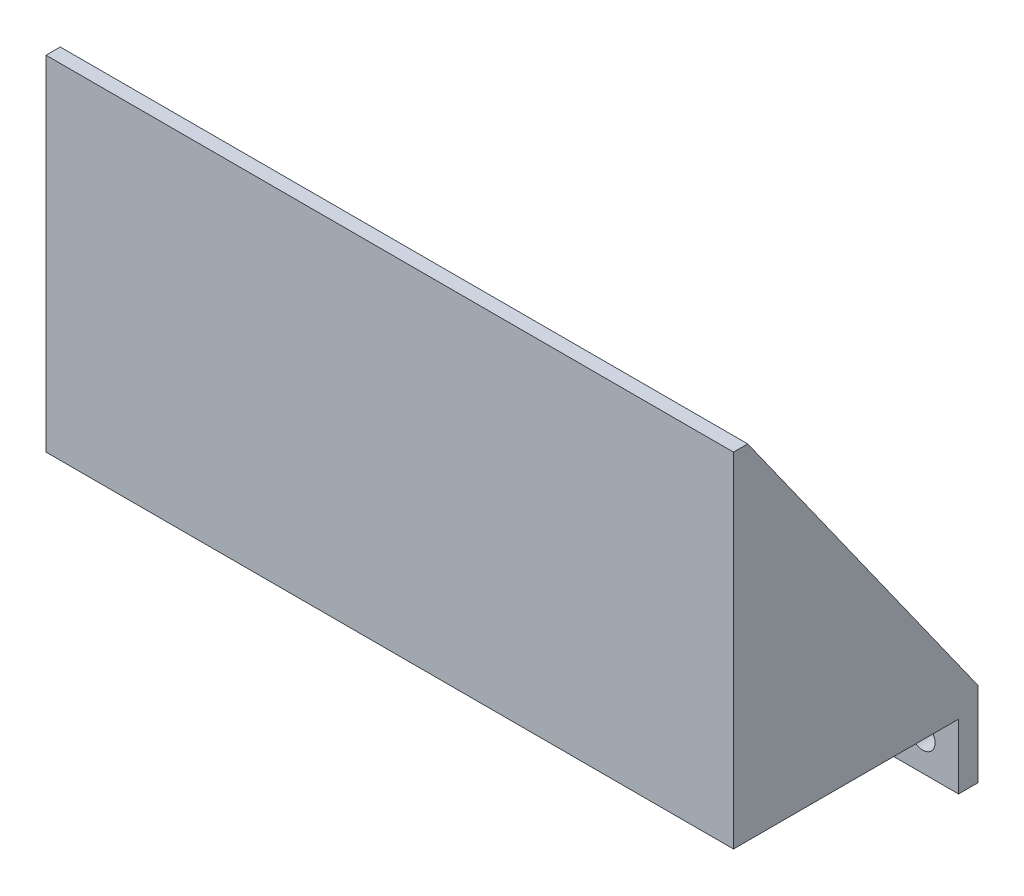
SolidWorks part; units mm, degrees
ref_plane "Front Plane" through (0, 0, 0) normal (0, 0, 1) x (1, 0, 0)
ref_plane "Top Plane" through (0, 0, 0) normal (0, 1, 0) x (1, 0, 0)
ref_plane "Right Plane" through (0, 0, 0) normal (1, 0, 0) x (0, 0, -1)
sketch "Sketch1" plane through (0, 0, 0) normal (0, 1, 0) x (1, 0, 0)
  line L0 (-3, 35.5) -> (0, 35.5)
  line L1 (0, 0) -> (100.5, 0)
  line L2 (0, 0) -> (0, 35.5)
  line L3 (0, 35.5) -> (100.5, 35.5)
  line L4 (100.5, 0) -> (100.5, 35.5)
  line L5 (-3, 35.5) -> (-3, -2.1974)
  line L6 (-3, -2.1974) -> (103, -2.1974)
  line L10 (103, 35.5) -> (100.5, 35.5)
  line L11 (103, 35.5) -> (103, -2.1974)
  line L12 (0, 35.5) -> (0, 0)
  line L13 (-3, 35.5) -> (103, 35.5)
  line L14 (-3, 35.5) -> (-3, 32.5)
  line L15 (-3, 32.5) -> (103, 32.5)
  line L16 (103, 35.5) -> (103, 32.5)
  line L17 (100.5, 35.5) -> (100.5, 0)
  line L19 (0, 35.5) -> (-3, 35.5)
  line L20 (0, 35.5) -> (0, 32.5)
  line L21 (0, 32.5) -> (-3, 32.5)
  line L22 (-3, 35.5) -> (-3, 32.5)
  line L23 (100.5, 35.5) -> (103, 35.5)
  line L24 (100.5, 35.5) -> (100.5, 32.5)
  line L25 (100.5, 32.5) -> (103, 32.5)
  line L26 (103, 35.5) -> (103, 32.5)
  dimension "D1" = 100.5
  dimension "D2" = 3
  dimension "D3" = 35.5
extrude "Boss-Extrude1" add sketch "Sketch1" along normal blind 50 contours L11 L10 L4 L1 L2 L0 L5 L6 | L20 L19 L22 L21 | L24 L23 L26 L25 region at (-1.5, 0, -31.3847)
sketch "Sketch2" plane through (0, 0, 0) normal (1, 0, 0) x (0, 0, -1)
  line L0 (35.5, 0) -> (0, 50)
  line L1 (0, 50) -> (35.5, 50)
  line L2 (35.5, 50) -> (35.5, 0)
extrude "Cut-Extrude1" cut sketch "Sketch2" against normal blind 10 and the other way blind 110
extrude "Boss-Extrude4" add sketch "Sketch1<6>" against normal blind 13 separate body contours L12 L15 L4 L3 | L5 L15 L12 L0 | L4 L15 L11 L10 region at (-1.5, 0, -34) region at (50.25, 0, -34) region at (101.75, 0, -34)
sketch "Sketch1<6>" plane through (0, 0, 0) normal (0, 1, 0) x (1, 0, 0) same geometry as "Sketch1"
extrude "Boss-Extrude5" add sketch "Sketch1<8>" against normal blind 3 contours L15 L2 L1 L4 | L15 L5 L6 L11 L4 L1 L2 region at (-1.5, 0, -31.3847) region at (50.25, 0, -16.25)
sketch "Sketch1<8>" plane through (0, 0, 0) normal (0, 1, 0) x (1, 0, 0) same geometry as "Sketch1"
sketch "Sketch3" plane through (0, 0, -32.5) normal (0, 0, 1) x (1, 0, 0)
  line L0 (50, -13) -> (50, -3) construction
  line L1 (-3, -13) -> (103, -13) construction
  line L2 (-3, -3) -> (103, -3) construction
  circle A0 centre (2.5143, -8) radius 1.9
  circle A2 centre (97.4857, -8) radius 1.9
extrude "Cut-Extrude2" cut sketch "Sketch3" against normal up to surface (3 mm away) up to face at (50.0833, -4.3333, -35.5)
